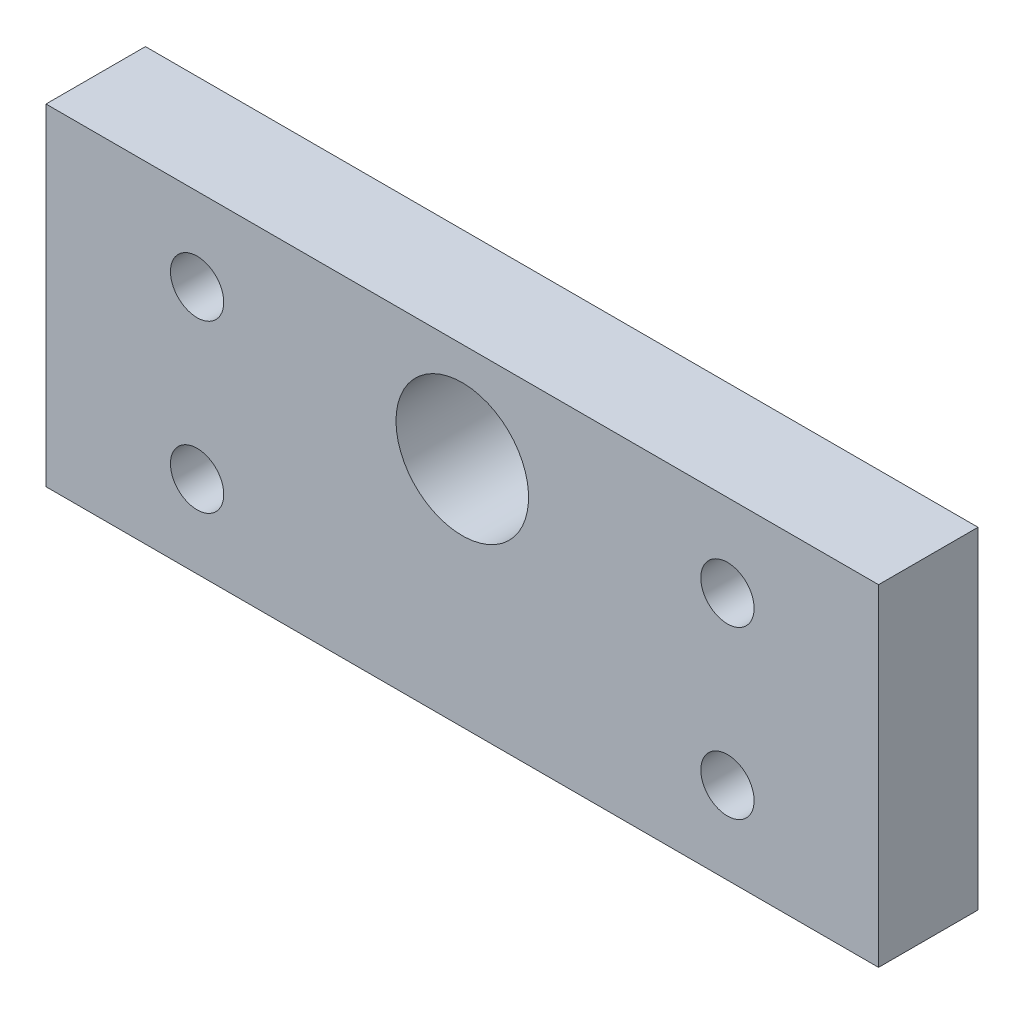
SolidWorks part; units mm, degrees
material "6061-T6 (SS)"
ref_plane "Front Plane" through (0, 0, 0) normal (0, 0, 1) x (1, 0, 0)
ref_plane "Top Plane" through (0, 0, 0) normal (0, 1, 0) x (1, 0, 0)
ref_plane "Right Plane" through (0, 0, 0) normal (1, 0, 0) x (0, 0, -1)
sketch "Sketch1" plane through (0, 0, 0) normal (0, 0, 1) x (1, 0, 0)
  line L2 (39.8731, 0) -> (-39.8731, 0)
  line L3 (39.8731, 0) -> (39.8731, 31.75)
  line L4 (39.8731, 31.75) -> (-39.8731, 31.75)
  line L6 (-39.8731, 0) -> (-39.8731, 31.75)
  circle A0 centre (0, 22.225) radius 6.35
  point P6 (0, 0)
  line B0 (63.5, 0) -> (63.5, 15.875)
  line B1 (63.5, 15.875) -> (36.5092, 15.875)
  line B2 (36.5092, 15.875) -> (47.625, 31.75)
  line B3 (47.625, 31.75) -> (16.0563, 31.75)
  line B4 (-16.0563, 31.75) -> (-16.0563, 12.7)
  line B5 (16.0563, 12.7) -> (16.0563, 31.75)
  line B6 (-63.5, 47.625) -> (63.5, 47.625)
  line B7 (63.5, 47.625) -> (63.5, 15.875)
  line B8 (0, 47.625) -> (0, 0) construction
  line B9 (-36.5092, 15.875) -> (36.5092, 15.875) construction
  line B10 (-28.702, 36.957) -> (28.702, 36.957) construction
  line B11 (-25.4, 7.874) -> (25.4, 7.874) construction
  line B12 (-25.4, 7.874) -> (-25.4, 23.8125) construction
  line B13 (25.4, 7.874) -> (25.4, 23.8125) construction
  line B14 (-52.832, 23.8125) -> (52.832, 23.8125) construction
  circle B15 centre (0, 22.225) radius 18.669 construction
  dimension "D1" = 12.7
sketch_block_instance "dovetail pair-1"
sketch_block "dovetail pair" parameters "D8"=37.338, "D1"=55, "D2"=127, "D3"=6.35, "D4"=15.875, "D5"=31.75, "D6"=95.25, "D7"=19.05, "D9"=55, "D10"=31.75, "D11"=50.8, "D12"=23.876, "D13"=7.874, "D14"=10.668, "D15"=34.798, "D16"=21.082, "D17"=7.9375
extrude "Boss-Extrude1" add sketch "Sketch1" along normal blind 9.525
hole_wizard "CBORE for #10 Socket Head Cap Screw1" positions "Sketch2" profile "Sketch3" counterbore size "#10" standard "ANSI Inch" end condition up to next
sketch "Sketch2" plane through (0, 0, 0) normal (0, 0, 1) x (1, 0, 0)
  point P27 (25.4, 23.8125)
  point P29 (-25.4, 23.8125)
  point P31 (-25.4, 7.874)
  point P33 (25.4, 7.874)
sketch "Sketch3" plane through (25.4, 23.8125, 0) normal (1, 0, 0) x (0, 1, 0)
  line L0 (0, 0) -> (0, 9.525)
  line L1 (0, 9.525) -> (2.5527, 9.525)
  line L3 (2.5527, 9.525) -> (2.5527, 4.826)
  line L4 (4.7625, 4.826) -> (2.5527, 4.826)
  line L5 (4.7625, 4.826) -> (4.7625, 0.635)
  line L6 (4.7625, 0.635) -> (5.3975, 0)
  line L7 (5.3975, 0) -> (0, 0)
  line L8 (-4.7625, 0.635) -> (-5.3975, 0) construction
  line L11 (0, -6.35) -> (0, 107.95) construction
  dimension "Thru Hole Dia." = 5.1054
  dimension "Thru Hole Depth" = 9.525
  dimension "C'Bore Dia." = 9.525
  dimension "C'Bore Depth" = 4.826
  dimension "Near C'Sink Dia." = 10.795
  dimension "Near C'Sink Angle" = 90
ref_plane "center plane" through (0, 0, 0) normal (1, 0, 0) x (0, 0, -1)
equation "\"dovetail-angle\" = 55"
equation "\"dovetail-stock-width\" = 5"
equation "\"dovetail-stock-height\" = 1.25"
equation "\"dovetail-depth\" = 0.5 * \"dovetail-stock-height\""
equation "\"dovetail-throat-width\" = \"dovetail-stock-width\" - (2 * \"dovetail-depth\")"
equation "\"delta-x\" = 6"
equation "\"delta-y\" = 3"
equation "\"gib-thickness\" = 0.25"
equation "\"x-slide-length\" = \"dovetail-stock-width\" + \"delta-x\""
equation "\"y-slide-length\" = \"dovetail-stock-width\" + \"delta-y\""
equation "\"dog-point-diam\" = .149"
equation "\"dog-point-length\" = .067"
equation "\"dovetail-double-height\" = 2 * \"dovetail-depth\" + 0.5"
equation "\"acme-major-diam\" = .5"
equation "\"acme-pitch-diam\" = 0.45"
equation "\"acme-minor-diam\" = 0.4"
equation "\"acme-nut-od\" = 1.47"
equation "\"acme-nut-length\" = 1"
equation "\"acme-nut-trim-height\" = .75"
equation "\"screw-bearing-od\" = 0.5"
equation "\"screw-bearing-length\" = .375"
equation "\"screw-bearing-id\" = .375"
equation "\"end-plate-thickness\" = \"screw-bearing-length\""
equation "\"screw-add-length\" = 2 * \"end-plate-thickness\" + 1 + 0.5"
equation "\"x-screw-length\" = \"x-slide-length\" + \"screw-add-length\""
equation "\"y-screw-length\" = \"y-slide-length\" + \"screw-add-length\""
equation "\"acme-nut-mount-hole-space-horz\" = 0.95"
equation "\"acme-nut-mount-hole-space-vert\" = 0.5 * \"acme-nut-length\""
equation "\"vise-hole-center-dist\" = 6.75"
equation "\"wiper_plate_clearance\" = .03"
equation "\"D1@Boss-Extrude1\"=\"screw-bearing-length\""
equation "\"D2@dovetail pair\"=\"dovetail-stock-width\""
equation "\"D1@dovetail pair\"=\"dovetail-angle\""
equation "\"D3@dovetail pair\"=\"gib-thickness\""
equation "\"D4@dovetail pair\"=\"dovetail-depth\""
equation "\"D5@dovetail pair\"=\"dovetail-stock-height\""
equation "\"D6@dovetail pair\"=\"dovetail-throat-width\""
equation "\"D10@dovetail pair\"=\"dovetail-stock-height\""
equation "\"D7@dovetail pair\"=\"acme-nut-trim-height\""
equation "\"D8@dovetail pair\"=\"acme-nut-od\""
equation "\"D9@dovetail pair\"=\"dovetail-angle\""
equation "\"D17@dovetail pair\"=\"dovetail-depth\"/2"
equation "\"D1@Sketch1\"=\"screw-bearing-od\""
